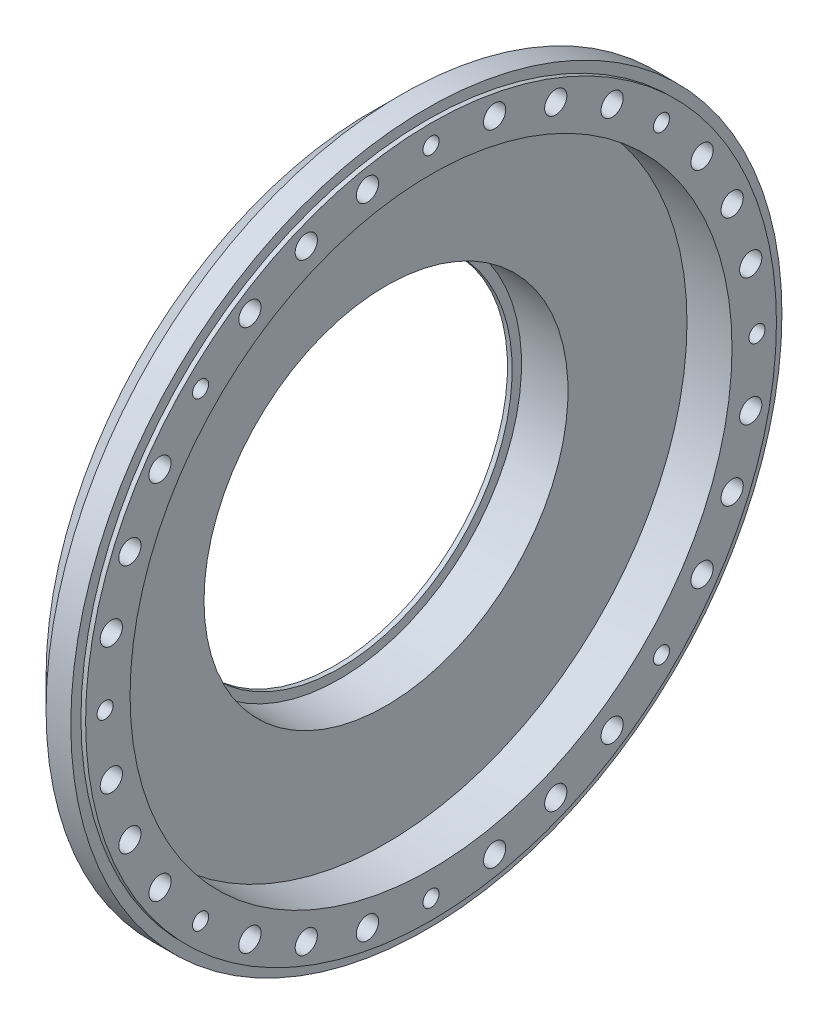
SolidWorks part; units mm, degrees
ref_plane "Front Plane" through (0, 0, 0) normal (0, 0, 1) x (1, 0, 0)
ref_plane "Top Plane" through (0, 0, 0) normal (0, 1, 0) x (1, 0, 0)
ref_plane "Right Plane" through (0, 0, 0) normal (1, 0, 0) x (0, 0, -1)
sketch "Sketch2" plane through (0, 0, 0) normal (0, 0, 1) x (1, 0, 0)
  line L0 (0, 0) -> (58.591, 0) construction
  line L2 (0, 0) -> (18.4, 0)
  line L3 (0, 0) -> (0, 2.5)
  line L4 (0, 2.5) -> (18.4, 2.5)
  line L5 (18.4, 0) -> (18.4, 2.5)
  line L6 (6, 2.5) -> (6, 6)
  line L11 (6, 6) -> (9.97, 6)
  line L16 (12.97, 6) -> (12.97, 3)
  line L17 (12.97, 3) -> (13.6304, 3)
  line L18 (13.6304, 3) -> (13.6304, 2.5)
  line L19 (13.6304, 2.5) -> (6, 2.5)
  line L22 (13.6304, 2.5) -> (16.1104, 2.5)
  line L23 (13.6304, 2.5) -> (13.6304, 4)
  line L24 (13.6304, 4) -> (16.1104, 4)
  line L25 (16.1104, 2.5) -> (16.1104, 4)
  line L27 (6, 6) -> (9.97, 6)
  line L28 (6, 6) -> (6, 9)
  line L29 (6, 9) -> (9.97, 9)
  line L30 (9.97, 6) -> (9.97, 9)
  line L31 (6, 9) -> (6, 8.25)
  line L32 (6, 8.25) -> (5, 8.25)
  line L33 (8.58, 22.001) -> (8.58, 12.476) construction
  line L34 (5, 12.476) -> (12.16, 12.476)
  line L35 (9.97, 9) -> (12.16, 9)
  line L36 (5, 7.5) -> (3, 7.5)
  line L37 (5, 8.25) -> (5, 12.476)
  line L38 (5, 7.5) -> (5, 14)
  line L39 (5, 14) -> (3, 14)
  line L40 (3, 7.5) -> (3, 14)
  line L41 (5, 22.001) -> (12.16, 22.001)
  line L42 (5, 22.001) -> (5, 30.1625)
  line L43 (5, 30.1625) -> (12.16, 30.1625)
  line L44 (12.16, 22.001) -> (12.16, 30.1625)
  line L49 (16.6304, 22.001) -> (16.6304, 7.5)
  line L51 (23.0104, 7.5) -> (23.0104, 6.5)
  line L54 (16.1104, 4) -> (13.6304, 4)
  line L56 (18.0304, 7.5) -> (23.0104, 7.5)
  line L57 (13.16, 22.001) -> (16.6304, 22.001)
  line L58 (16.1104, 3.5) -> (20.0104, 3.5)
  line L59 (29.9004, 14) -> (26.9004, 11)
  line L60 (4, 31.75) -> (18.0304, 31.75)
  line L61 (18.0304, 7.5) -> (23.0104, 7.5)
  line L62 (18.0304, 7.5) -> (18.0304, 12)
  line L63 (18.0304, 12) -> (23.0104, 12)
  line L64 (23.0104, 7.5) -> (23.0104, 12)
  line L65 (18.0304, 31.75) -> (18.0304, 12)
  line L66 (23.0104, 11) -> (26.9004, 11)
  line L67 (34.8004, 23) -> (31.3004, 19.5)
  line L68 (35.8004, 31) -> (38.7904, 33.99)
  line L69 (29.9004, 14) -> (29.9004, 15)
  line L70 (29.9004, 15) -> (22.9304, 15)
  line L71 (22.9304, 15) -> (21.0304, 15)
  line L72 (18.0304, 7.5) -> (16.6304, 7.5)
  line L73 (21.0304, 15) -> (21.0304, 43)
  line L74 (20.0304, 40) -> (10.0704, 40)
  line L75 (10.0704, 40) -> (4, 40)
  line L76 (21.0304, 43) -> (20.0304, 43)
  line L77 (22.9304, 15) -> (29.9004, 15)
  line L78 (22.9304, 15) -> (22.9304, 21)
  line L79 (22.9304, 21) -> (29.9004, 21)
  line L80 (29.9004, 15) -> (29.9004, 21)
  line L81 (10.0704, 40) -> (20.0304, 40)
  line L82 (10.0704, 40) -> (10.0704, 50)
  line L83 (10.0704, 50) -> (20.0304, 50)
  line L84 (20.0304, 40) -> (20.0304, 50)
  line L85 (4, 40) -> (4, 31.75)
  line L86 (12.97, 3) -> (12.97, 2.5)
  line L87 (31.3004, 19.5) -> (29.9004, 19.5)
  line L88 (21.51, 63.5) -> (21.51, 44)
  line L89 (21.51, 63.5) -> (25.9304, 63.5)
  line L90 (25.9304, 63.5) -> (25.9304, 25)
  line L91 (27.8304, 25) -> (25.9304, 25)
  line L92 (10.0704, 48) -> (9, 48)
  line L93 (9, 48) -> (9, 53.476)
  line L94 (9, 53.476) -> (20.0304, 53.476)
  line L95 (20.0304, 53.476) -> (20.0304, 50)
  line L96 (14.5152, 63.001) -> (14.5152, 53.476) construction
  line L97 (9, 63.001) -> (20.0304, 63.001)
  line L98 (9, 63.001) -> (9, 68.2625)
  line L99 (9, 68.2625) -> (20.0304, 68.2625)
  line L100 (20.0304, 63.001) -> (20.0304, 68.2625)
  line L101 (12.97, 6) -> (11.97, 6)
  line L102 (9, 42.5) -> (5, 42.5)
  line L103 (9, 42.5) -> (9, 55)
  line L104 (9, 55) -> (5, 55)
  line L105 (5, 42.5) -> (5, 55)
  line L106 (9.97, 6) -> (10.87, 6)
  line L107 (27.8304, 25) -> (34.8004, 25)
  line L108 (34.8004, 25) -> (34.8004, 23)
  line L109 (0, 0) -> (-2, 0)
  line L110 (0, 0) -> (0, 11)
  line L111 (27.8304, 25) -> (34.8004, 25)
  line L112 (27.8304, 25) -> (27.8304, 32.5)
  line L113 (27.8304, 32.5) -> (34.8004, 32.5)
  line L114 (34.8004, 25) -> (34.8004, 32.5)
  line L115 (35.8004, 31) -> (34.8004, 31)
  line L116 (27.8304, 32.5) -> (27.8304, 64.5)
  line L117 (21.1827, 74.025) -> (6.8477, 74.025)
  line L118 (6.8477, 74.025) -> (6.8477, 76.2)
  line L119 (38.7904, 47.29) -> (30.8304, 55.25)
  line L120 (0, 11) -> (-2, 11)
  line L121 (38.7904, 43.815) -> (30.8529, 43.815)
  line L123 (-4.8, 69.85) -> (1.55, 76.2)
  line L124 (38.7904, 47.29) -> (38.7904, 33.99)
  line L125 (-2, 0) -> (-2, 11)
  line L126 (38.7904, 37.465) -> (30.8529, 37.465)
  line L127 (30.8529, 43.815) -> (30.8529, 37.465)
  line L128 (6, 2.5) -> (6, 0)
  line L129 (0, 63.5) -> (0, 30)
  line L132 (5, 63.5) -> (0, 63.5)
  line L136 (-1.8, 30) -> (-11.76, 30)
  line L138 (-13.76, 25.4) -> (-2, 25.4)
  line L139 (-2, 25.4) -> (-2, 11.5)
  line L140 (27.8304, 64.5) -> (21.1827, 64.5)
  line L141 (-1.8, 30) -> (-11.76, 30)
  line L142 (-1.8, 30) -> (-1.8, 39)
  line L143 (-1.8, 39) -> (-11.76, 39)
  line L144 (-11.76, 30) -> (-11.76, 39)
  line L145 (21.1827, 64.5) -> (21.1827, 74.025)
  line L146 (-12.76, 37) -> (-12.76, 47.29)
  line L147 (-12.76, 37) -> (-11.76, 37)
  line L148 (30.8304, 55.25) -> (30.8304, 76.2)
  line L149 (11.97, 6) -> (11.97, 5.45)
  line L154 (-2, 11.5) -> (1, 11.5)
  line L155 (5, 60.6197) -> (24.05, 60.6197)
  line L160 (5, 60.6197) -> (5, 55.8572)
  line L161 (5, 55.8572) -> (24.05, 55.8572)
  line L166 (24.05, 60.6197) -> (24.05, 55.8572)
  line L167 (5, 60.6197) -> (24.05, 55.8572) construction
  line L172 (5, 55.8572) -> (24.05, 60.6197) construction
  line L173 (24.05, 62.2072) -> (25.9304, 62.2072)
  line L174 (11.97, 5.45) -> (10.87, 5.45)
  line L175 (10.87, 6) -> (10.87, 5.45)
  line L176 (24.05, 62.2072) -> (24.05, 54.2697)
  line L177 (24.05, 54.2697) -> (25.9304, 54.2697)
  line L178 (25.9304, 62.2072) -> (25.9304, 54.2697)
  line L179 (24.05, 62.2072) -> (25.9304, 54.2697) construction
  line L180 (24.05, 54.2697) -> (25.9304, 62.2072) construction
  line L181 (3, 19.6197) -> (15.7, 19.6197)
  line L182 (3, 19.6197) -> (3, 14.8572)
  line L183 (3, 14.8572) -> (15.7, 14.8572)
  line L184 (15.7, 19.6197) -> (15.7, 14.8572)
  line L185 (3, 19.6197) -> (15.7, 14.8572) construction
  line L186 (3, 14.8572) -> (15.7, 19.6197) construction
  line L187 (15.7, 21.2072) -> (16.6304, 21.2072)
  line L188 (15.7, 21.2072) -> (15.7, 13.2697)
  line L189 (15.7, 13.2697) -> (16.6304, 13.2697)
  line L190 (16.6304, 21.2072) -> (16.6304, 13.2697)
  line L191 (15.7, 21.2072) -> (16.6304, 13.2697) construction
  line L192 (15.7, 13.2697) -> (16.6304, 21.2072) construction
  line L193 (1, 11.5) -> (1, 6.5)
  line L194 (1, 6.5) -> (3, 6.5)
  line L195 (23.0104, 6.5) -> (20.0104, 3.5)
  line L196 (5, 63.5) -> (5, 42.5)
  line L197 (5, 42.5) -> (3, 42.5)
  line L198 (3, 42.5) -> (3, 6.5)
  line L199 (6, 0) -> (12.97, 0)
  line L200 (12.97, 0) -> (12.97, 2.5)
  line L201 (18.0304, 31.75) -> (18.0304, 35.875)
  line L202 (18.0304, 35.875) -> (21.0304, 35.875)
  line L203 (30.8304, 76.2) -> (6.8477, 76.2)
  line L204 (3.4027, 69.85) -> (7.8477, 69.85) construction
  line L205 (7.8477, 67.4687) -> (26.8977, 67.4688)
  line L206 (7.8477, 74.025) -> (7.8477, 64.5)
  line L207 (7.8477, 64.5) -> (-1.8, 64.5)
  line L208 (-1.8, 64.5) -> (-1.8, 39)
  line L209 (-12.76, 47.29) -> (-4.8, 55.25)
  line L210 (-4.8, 55.25) -> (-4.8, 69.85)
  line L211 (7.8477, 67.4687) -> (7.8477, 72.2313)
  line L212 (7.8477, 72.2313) -> (26.8977, 72.2313)
  line L213 (26.8977, 67.4688) -> (26.8977, 72.2313)
  line L214 (26.8977, 73.8187) -> (30.8304, 73.8187)
  line L215 (26.8977, 73.8187) -> (26.8977, 65.8813)
  line L216 (26.8977, 65.8813) -> (30.8304, 65.8813)
  line L217 (30.8304, 73.8187) -> (30.8304, 65.8813)
  line L218 (3.4027, 72.2313) -> (25.6277, 72.2313)
  line L219 (3.4027, 72.2313) -> (3.4027, 67.4687)
  line L220 (3.4027, 67.4687) -> (25.6277, 67.4687)
  line L221 (25.6277, 72.2313) -> (25.6277, 67.4687)
  line L222 (25.6277, 69.85) -> (21.1827, 69.85) construction
  line L223 (21.51, 44) -> (22.9304, 44)
  line L224 (22.9304, 44) -> (22.9304, 21)
  line L225 (13.6304, 4) -> (13.6304, 12.2697)
  line L226 (13.6304, 12.2697) -> (13.16, 12.2697)
  line L227 (13.16, 12.2697) -> (13.16, 22.001)
  line L228 (12.16, 9) -> (12.16, 12.476)
  line L229 (-1.8, 30) -> (0, 30)
  line L230 (9, 65.6317) -> (3.4027, 65.6317) construction
  line L231 (20.0304, 65.6317) -> (25.6277, 65.6317) construction
  line L232 (1.55, 76.2) -> (6.8477, 76.2)
  line L233 (-11.76, 30) -> (-13.76, 30)
  line L234 (-13.76, 30) -> (-13.76, 25.4)
  circle A0 centre (26.8804, 25.95) radius 0.95
  circle A1 centre (21.9804, 15.95) radius 0.95
  circle A2 centre (17.3304, 8.2) radius 0.7
  circle A3 centre (10.42, 6.45) radius 0.45
  circle A4 centre (-0.9, 30.9) radius 0.9
  point P7 (24.9902, 58.2385)
  point P131 (16.1652, 17.2385)
  point P135 (14.525, 58.2385)
  point P146 (9.35, 17.2385)
sketch "Sketch3" plane through (0, 0, 0) normal (1, 0, 0) x (0, 0, -1)
  line L0 (0, 0) -> (0, 69.85) construction
  line L1 (0, 0) -> (13.6271, 68.5079) construction
  line L2 (0, 0) -> (0, 58.2385) construction
  line L3 (0, 0) -> (50.436, 29.1192) construction
  line L4 (0, 0) -> (0, 31.75) construction
  line L5 (0, 0) -> (12.1502, 29.3332) construction
  line L6 (0, 0) -> (0, 17.2385) construction
  line L7 (0, 0) -> (14.929, 8.6192) construction
  line L8 (0, 0) -> (0, 58.2385) construction
  line L9 (0, 0) -> (50.436, 29.1192) construction
  line L10 (0, 0) -> (5.9583, 29.9542) construction
  line L11 (0, 0) -> (16.9677, 25.394) construction
  circle A0 centre (0, 0) radius 69.85 construction
  circle A1 centre (0, 0) radius 58.2385 construction
  circle A2 centre (0, 0) radius 31.75 construction
  circle A3 centre (0, 0) radius 17.2385 construction
  circle A4 centre (0, 69.85) radius 3.175
  circle A5 centre (0, 58.2385) radius 4.7625
  circle A6 centre (0, 31.75) radius 3.175
  circle A7 centre (0, 17.2385) radius 4.7625
  circle A8 centre (13.6271, 68.5079) radius 3.175
  circle A9 centre (26.7304, 64.533) radius 3.175
  circle A10 centre (38.8066, 58.0782) radius 3.175
  circle A11 centre (49.3914, 49.3914) radius 3.175
  circle A12 centre (58.0782, 38.8066) radius 3.175
  circle A13 centre (64.533, 26.7304) radius 3.175
  circle A14 centre (68.5079, 13.6271) radius 3.175
  circle A15 centre (69.85, 0) radius 3.175
  circle A16 centre (68.5079, -13.6271) radius 3.175
  circle A17 centre (64.533, -26.7304) radius 3.175
  circle A18 centre (58.0782, -38.8066) radius 3.175
  circle A19 centre (49.3914, -49.3914) radius 3.175
  circle A20 centre (38.8066, -58.0782) radius 3.175
  circle A21 centre (26.7304, -64.533) radius 3.175
  circle A22 centre (13.6271, -68.5079) radius 3.175
  circle A23 centre (0, -69.85) radius 3.175
  circle A24 centre (-13.6271, -68.5079) radius 3.175
  circle A25 centre (-26.7304, -64.533) radius 3.175
  circle A26 centre (-38.8066, -58.0782) radius 3.175
  circle A27 centre (-49.3914, -49.3914) radius 3.175
  circle A28 centre (-58.0782, -38.8066) radius 3.175
  circle A29 centre (-64.533, -26.7304) radius 3.175
  circle A30 centre (-68.5079, -13.6271) radius 3.175
  circle A31 centre (-69.85, 0) radius 3.175
  circle A32 centre (-68.5079, 13.6271) radius 3.175
  circle A33 centre (-64.533, 26.7304) radius 3.175
  circle A34 centre (-58.0782, 38.8066) radius 3.175
  circle A35 centre (-49.3914, 49.3914) radius 3.175
  circle A36 centre (-38.8066, 58.0782) radius 3.175
  circle A37 centre (-26.7304, 64.533) radius 3.175
  circle A38 centre (-13.6271, 68.5079) radius 3.175
  circle A47 centre (50.436, 29.1192) radius 4.7625
  circle A48 centre (50.436, -29.1192) radius 4.7625
  circle A49 centre (0, -58.2385) radius 4.7625
  circle A50 centre (-50.436, -29.1192) radius 4.7625
  circle A51 centre (-50.436, 29.1192) radius 4.7625
  circle A58 centre (12.1502, 29.3332) radius 3.175
  circle A59 centre (22.4506, 22.4506) radius 3.175
  circle A60 centre (29.3332, 12.1502) radius 3.175
  circle A61 centre (31.75, 0) radius 3.175
  circle A62 centre (29.3332, -12.1502) radius 3.175
  circle A63 centre (22.4506, -22.4506) radius 3.175
  circle A64 centre (12.1502, -29.3332) radius 3.175
  circle A65 centre (0, -31.75) radius 3.175
  circle A66 centre (-12.1502, -29.3332) radius 3.175
  circle A67 centre (-22.4506, -22.4506) radius 3.175
  circle A68 centre (-29.3332, -12.1502) radius 3.175
  circle A69 centre (-31.75, 0) radius 3.175
  circle A70 centre (-29.3332, 12.1502) radius 3.175
  circle A71 centre (-22.4506, 22.4506) radius 3.175
  circle A72 centre (14.929, 8.6192) radius 4.7625
  circle A73 centre (14.929, -8.6192) radius 4.7625
  circle A74 centre (0, -17.2385) radius 4.7625
  circle A75 centre (-14.929, -8.6192) radius 4.7625
  circle A76 centre (-14.929, 8.6192) radius 4.7625
  circle A77 centre (0, 0) radius 50
  circle A78 centre (0, 0) radius 9
  circle A79 centre (-12.1502, 29.3332) radius 3.175
  circle A80 centre (0, 0) radius 76.2
  circle A81 centre (0, 0) radius 74.025
  circle A82 centre (0, 69.85) radius 3.9687
  circle A83 centre (49.3914, 49.3914) radius 3.9687
  circle A84 centre (69.85, 0) radius 3.9688
  circle A85 centre (49.3914, -49.3914) radius 3.9687
  circle A86 centre (0, -69.85) radius 3.9687
  circle A87 centre (-49.3914, -49.3914) radius 3.9687
  circle A88 centre (-69.85, 0) radius 3.9688
  circle A89 centre (-49.3914, 49.3914) radius 3.9687
  circle A90 centre (0, 69.85) radius 2.3812
  circle A91 centre (13.6271, 68.5079) radius 2.3812
  circle A92 centre (26.7304, 64.533) radius 2.3813
  circle A93 centre (38.8066, 58.0782) radius 2.3812
  circle A94 centre (49.3914, 49.3914) radius 2.3812
  circle A95 centre (58.0782, 38.8066) radius 2.3812
  circle A96 centre (64.533, 26.7304) radius 2.3813
  circle A97 centre (68.5079, 13.6271) radius 2.3813
  circle A98 centre (69.85, 0) radius 2.3813
  circle A99 centre (68.5079, -13.6271) radius 2.3813
  circle A100 centre (64.533, -26.7304) radius 2.3813
  circle A101 centre (58.0782, -38.8066) radius 2.3812
  circle A102 centre (49.3914, -49.3914) radius 2.3812
  circle A103 centre (38.8066, -58.0782) radius 2.3812
  circle A104 centre (26.7304, -64.533) radius 2.3813
  circle A105 centre (13.6271, -68.5079) radius 2.3812
  circle A106 centre (0, -69.85) radius 2.3812
  circle A107 centre (-13.6271, -68.5079) radius 2.3812
  circle A108 centre (-26.7304, -64.533) radius 2.3813
  circle A109 centre (-38.8066, -58.0782) radius 2.3812
  circle A110 centre (-49.3914, -49.3914) radius 2.3812
  circle A111 centre (-58.0782, -38.8066) radius 2.3812
  circle A112 centre (-64.533, -26.7304) radius 2.3812
  arc A113 (3.0399, 30.8338) -> (8.9911, 29.65) centre (5.9583, 29.9542) cw
  arc A114 (14.6081, 27.3234) -> (19.6532, 23.9523) centre (16.9677, 25.394) cw
  arc A115 (23.9523, 19.6532) -> (27.3234, 14.6081) centre (25.394, 16.9677) cw
  arc A116 (29.65, 8.9911) -> (30.8338, 3.0399) centre (29.9542, 5.9583) cw
  arc A117 (30.8338, -3.0399) -> (29.65, -8.9911) centre (29.9542, -5.9583) cw
  arc A118 (27.3234, -14.6081) -> (23.9523, -19.6532) centre (25.394, -16.9677) cw
  arc A119 (19.6532, -23.9523) -> (14.6081, -27.3234) centre (16.9677, -25.394) cw
  arc A120 (8.9911, -29.65) -> (3.0399, -30.8338) centre (5.9583, -29.9542) cw
  arc A121 (-3.0399, -30.8338) -> (-8.9911, -29.65) centre (-5.9583, -29.9542) cw
  arc A122 (-14.6081, -27.3234) -> (-19.6532, -23.9523) centre (-16.9677, -25.394) cw
  arc A123 (-23.9523, -19.6532) -> (-27.3234, -14.6081) centre (-25.394, -16.9677) cw
  arc A124 (-29.65, -8.9911) -> (-30.8338, -3.0399) centre (-29.9542, -5.9583) cw
  arc A125 (-30.8338, 3.0399) -> (-29.65, 8.9911) centre (-29.9542, 5.9583) cw
  arc A126 (-27.3234, 14.6081) -> (-23.9523, 19.6532) centre (-25.394, 16.9677) cw
  arc A127 (-19.6532, 23.9523) -> (-14.6081, 27.3234) centre (-16.9677, 25.394) cw
  arc A128 (-8.9911, 29.65) -> (-3.0399, 30.8338) centre (-5.9583, 29.9542) cw
  arc A129 (26.9875, 0) -> (26.9932, 0.1932) centre (30.2705, 0) cw
  arc A130 (65.0988, 0.2771) -> (65.0875, 0) centre (68.4964, 0) ccw
  circle A131 centre (1.5875, 0) radius 40
  circle A132 centre (1.5875, 0) radius 2.5
  circle A133 centre (1.5875, 0) radius 3
  circle A134 centre (1.5875, 0) radius 43
  circle A135 centre (-68.5079, -13.6271) radius 2.3813
  circle A136 centre (-69.85, 0) radius 2.3813
  circle A137 centre (-68.5079, 13.6271) radius 2.3813
  circle A138 centre (-64.533, 26.7304) radius 2.3812
  circle A139 centre (-58.0782, 38.8066) radius 2.3812
  circle A140 centre (-49.3914, 49.3914) radius 2.3812
  circle A141 centre (-38.8066, 58.0782) radius 2.3812
  circle A142 centre (-26.7304, 64.533) radius 2.3813
  circle A143 centre (-13.6271, 68.5079) radius 2.3812
  circle A144 centre (0, 58.2385) radius 2.3812
  circle A145 centre (0, 58.2385) radius 3.9688
  circle A146 centre (50.436, 29.1192) radius 3.9688
  circle A147 centre (50.436, 29.1192) radius 2.3813
  circle A148 centre (50.436, -29.1192) radius 3.9687
  circle A149 centre (50.436, -29.1192) radius 2.3812
  circle A150 centre (0, -58.2385) radius 3.9687
  circle A151 centre (0, -58.2385) radius 2.3812
  circle A152 centre (-50.436, -29.1192) radius 3.9687
  circle A153 centre (-50.436, -29.1192) radius 2.3812
  circle A154 centre (-50.436, 29.1192) radius 3.9687
  circle A155 centre (-50.436, 29.1192) radius 2.3812
  spline S1 degree 4 number of poles 499 (26.9875, 0) -> (26.9932, 0.1932)
  spline S3 degree 4 number of poles 617 (65.0875, 0) -> (65.0988, 0.2771)
  point P116 (0, 0)
  point P225 (0, 0)
sketch "Sketch4" plane through (0, 0, 0) normal (0, 0, 1) x (1, 0, 0)
  line L0 (21.1827, 74.025) -> (6.8477, 74.025) construction
  line L1 (6.8477, 74.025) -> (6.8477, 76.2) construction
  line L2 (7.8477, 74.025) -> (7.8477, 64.5) construction
  line L3 (7.8477, 64.5) -> (-1.8, 64.5) construction
  line L4 (-1.8, 64.5) -> (-1.8, 39) construction
  line L5 (-11.76, 30) -> (-11.76, 39) construction
  line L6 (-1.8, 39) -> (-11.76, 39) construction
  line L7 (-12.76, 37) -> (-11.76, 37) construction
  line L8 (-12.76, 37) -> (-12.76, 47.29) construction
  line L9 (-12.76, 47.29) -> (-4.8, 55.25) construction
  line L10 (-4.8, 55.25) -> (-4.8, 69.85) construction
  line L12 (7.8477, 74.025) -> (6.8477, 74.025)
  line L13 (6.8477, 74.025) -> (6.8477, 76.2)
  line L14 (7.8477, 74.025) -> (7.8477, 64.5)
  line L15 (7.8477, 64.5) -> (-1.8, 64.5)
  line L16 (-1.8, 64.5) -> (-1.8, 39)
  line L17 (-11.76, 37) -> (-11.76, 39)
  line L18 (-1.8, 39) -> (-11.76, 39)
  line L19 (-12.76, 37) -> (-11.76, 37)
  line L20 (-12.76, 37) -> (-12.76, 47.29)
  line L21 (-12.76, 47.29) -> (-4.8, 55.25)
  line L22 (-4.8, 55.25) -> (-4.8, 69.85)
  line L24 (-4.8, 69.85) -> (1.55, 76.2) construction
  line L25 (1.55, 76.2) -> (6.8477, 76.2) construction
  line L26 (-4.8, 69.85) -> (1.55, 76.2)
  line L27 (1.55, 76.2) -> (6.8477, 76.2)
revolve "Revolve1" add sketch "Sketch4" angle 360 about L0
sketch "Sketch5" plane through (7.8477, 0, 0) normal (1, 0, 0) x (0, 0, -1)
  circle A0 centre (13.6271, 68.5079) radius 2.3812 construction
  circle A1 centre (26.7304, 64.533) radius 2.3813 construction
  circle A2 centre (38.8066, 58.0782) radius 2.3813 construction
  circle A3 centre (58.0782, 38.8066) radius 2.3812 construction
  circle A4 centre (64.533, 26.7304) radius 2.3813 construction
  circle A5 centre (68.5079, 13.6271) radius 2.3813 construction
  circle A6 centre (68.5079, -13.6271) radius 2.3813 construction
  circle A7 centre (64.533, -26.7304) radius 2.3813 construction
  circle A8 centre (58.0782, -38.8066) radius 2.3813 construction
  circle A9 centre (38.8066, -58.0782) radius 2.3812 construction
  circle A10 centre (26.7304, -64.533) radius 2.3813 construction
  circle A11 centre (13.6271, -68.5079) radius 2.3812 construction
  circle A12 centre (-13.6271, -68.5079) radius 2.3812 construction
  circle A13 centre (-26.7304, -64.533) radius 2.3813 construction
  circle A14 centre (-38.8066, -58.0782) radius 2.3812 construction
  circle A15 centre (-58.0782, -38.8066) radius 2.3812 construction
  circle A16 centre (-64.533, -26.7304) radius 2.3813 construction
  circle A17 centre (-68.5079, -13.6271) radius 2.3813 construction
  circle A18 centre (-68.5079, 13.6271) radius 2.3813 construction
  circle A19 centre (-64.533, 26.7304) radius 2.3813 construction
  circle A20 centre (-58.0782, 38.8066) radius 2.3813 construction
  circle A21 centre (-38.8066, 58.0782) radius 2.3812 construction
  circle A22 centre (-26.7304, 64.533) radius 2.3813 construction
  circle A23 centre (-13.6271, 68.5079) radius 2.3812 construction
  circle A24 centre (13.6271, 68.5079) radius 2.3812
  circle A25 centre (26.7304, 64.533) radius 2.3813
  circle A26 centre (38.8066, 58.0782) radius 2.3812
  circle A27 centre (58.0782, 38.8066) radius 2.3812
  circle A28 centre (64.533, 26.7304) radius 2.3813
  circle A29 centre (68.5079, 13.6271) radius 2.3813
  circle A30 centre (68.5079, -13.6271) radius 2.3813
  circle A31 centre (64.533, -26.7304) radius 2.3813
  circle A32 centre (58.0782, -38.8066) radius 2.3812
  circle A33 centre (38.8066, -58.0782) radius 2.3812
  circle A34 centre (26.7304, -64.533) radius 2.3813
  circle A35 centre (13.6271, -68.5079) radius 2.3812
  circle A36 centre (-13.6271, -68.5079) radius 2.3812
  circle A37 centre (-26.7304, -64.533) radius 2.3813
  circle A38 centre (-38.8066, -58.0782) radius 2.3812
  circle A39 centre (-58.0782, -38.8066) radius 2.3812
  circle A40 centre (-64.533, -26.7304) radius 2.3812
  circle A41 centre (-68.5079, -13.6271) radius 2.3813
  circle A42 centre (-68.5079, 13.6271) radius 2.3813
  circle A43 centre (-64.533, 26.7304) radius 2.3812
  circle A44 centre (-58.0782, 38.8066) radius 2.3812
  circle A45 centre (-38.8066, 58.0782) radius 2.3812
  circle A46 centre (-26.7304, 64.533) radius 2.3813
  circle A47 centre (-13.6271, 68.5079) radius 2.3812
extrude "Cut-Extrude1" cut sketch "Sketch5" against normal up to vertex (4.445 mm away) up to point (3.4027, 72.2313, 0)
sketch "Sketch6" plane through (7.8477, 0, 0) normal (1, 0, 0) x (0, 0, -1)
  circle A0 centre (49.3914, -49.3914) radius 3.9688 construction
  circle A1 centre (0, 0) radius 74.025
  circle A2 centre (0, 0) radius 74.025
  circle A3 centre (69.85, 0) radius 3.9688 construction
  circle A4 centre (49.3914, 49.3914) radius 3.9687 construction
  circle A5 centre (0, 69.85) radius 3.9687 construction
  circle A6 centre (-49.3914, 49.3914) radius 3.9687 construction
  circle A7 centre (-69.85, 0) radius 3.9688 construction
  circle A8 centre (-49.3914, -49.3914) radius 3.9688 construction
  circle A9 centre (0, -69.85) radius 3.9687 construction
  circle A10 centre (49.3914, -49.3914) radius 3.9687
  circle A11 centre (69.85, 0) radius 3.9688
  circle A12 centre (49.3914, 49.3914) radius 3.9687
  circle A13 centre (0, 69.85) radius 3.9687
  circle A14 centre (-49.3914, 49.3914) radius 3.9687
  circle A15 centre (-69.85, 0) radius 3.9688
  circle A16 centre (-49.3914, -49.3914) radius 3.9687
  circle A17 centre (0, -69.85) radius 3.9687
  circle A18 centre (0, 69.85) radius 1.7272
  circle A19 centre (49.3914, 49.3914) radius 1.7272
  circle A20 centre (69.85, 0) radius 1.7272
  circle A21 centre (49.3914, -49.3914) radius 1.7272
  circle A22 centre (0, -69.85) radius 1.7272
  circle A23 centre (-49.3914, -49.3914) radius 1.7272
  circle A24 centre (-69.85, 0) radius 1.7272
  circle A25 centre (-49.3914, 49.3914) radius 1.7272
  dimension "D2" = 3.4544
  dimension "D1" = 0
extrude "Cut-Extrude2" cut sketch "Sketch6" against normal blind 9.525 contours A18 | A25 | A24 | A23 | A22 | A21 | A20 | A19 region at (7.8477, 69.85, 0) region at (7.8477, 49.3914, -49.3914) region at (7.8477, 0, -69.85) region at (7.8477, -49.3914, -49.3914) region at (7.8477, -69.85, 0) region at (7.8477, -49.3914, 49.3914) region at (7.8477, 0, 69.85) region at (7.8477, 49.3914, 49.3914)
